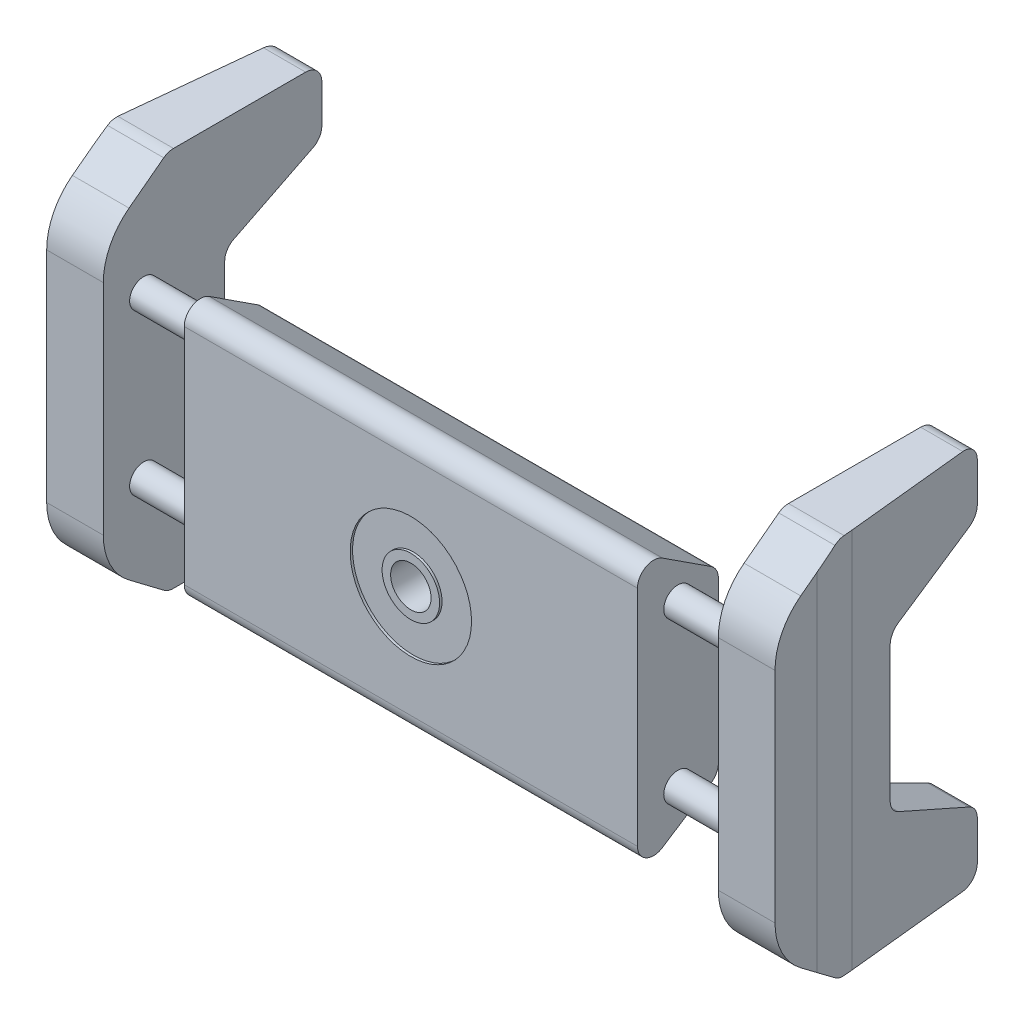
SolidWorks part; units mm, degrees
ref_plane "Front Plane" through (0, 0, 0) normal (0, 0, 1) x (1, 0, 0)
ref_plane "Top Plane" through (0, 0, 0) normal (0, 1, 0) x (1, 0, 0)
ref_plane "Right Plane" through (0, 0, 0) normal (1, 0, 0) x (0, 0, -1)
sketch "Sketch1" plane through (0, 0, 0) normal (1, 0, 0) x (0, 0, -1)
  line L0 (3.09, -2.0085) -> (9.09, -5.9085)
  line L2 (0, -3.6854) -> (0, -31.3146)
  line L4 (10, -7.5854) -> (10, -27.4146)
  line L5 (3.09, -32.9915) -> (9.09, -29.0915)
  arc A0 (3.09, -2.0085) -> (0, -3.6854) centre (2, -3.6854) ccw
  arc A1 (9.09, -5.9085) -> (10, -7.5854) centre (8, -7.5854) cw
  arc A2 (0, -31.3146) -> (3.09, -32.9915) centre (2, -31.3146) ccw
  arc A3 (9.09, -29.0915) -> (10, -27.4146) centre (8, -27.4146) ccw
  point P5 (0, 0)
  point P8 (0, 0)
  point P11 (10, -6.5)
  point P14 (0, -35)
  point P17 (10, -28.5)
  dimension "D1" = 2
  dimension "D2" = 35
  dimension "D3" = 22
extrude "Boss-Extrude1" add sketch "Sketch1" along normal blind 56
sketch "Sketch2" plane through (56, 0, 0) normal (1, 0, 0) x (0, 0, -1)
  line L0 (0, -17.5) -> (10, -17.5) construction
  line L1 (0, -3.6854) -> (0, -31.3146) construction
  line L2 (10, -27.4146) -> (10, -7.5854) construction
  line L3 (5, -32.8793) -> (5, -2.0411) construction
  line L4 (10, -7.5854) -> (0, -7.5854) construction
  circle A0 centre (5, -7.5854) radius 1.75
  circle A1 centre (5, -27.4146) radius 1.75
  dimension "D1" = 3.5
extrude "Boss-Extrude2" add sketch "Sketch2" along normal blind 10
ref_plane "Plane1" through (66, 0, 0) normal (1, 0, 0) x (0, 0, -1)
sketch "Sketch3" plane through (66, 0, 0) normal (1, 0, 0) x (0, 0, -1)
  line L0 (9.09, -5.9085) -> (0, 0) construction
  line L1 (25.8944, -32.4893) -> (16.1056, -27.5948)
  line L2 (10, -7.5854) -> (10, 4.7359) construction
  line L3 (3.1785, 2.4006) -> (7.465, 5.638)
  line L4 (8.6704, 6.0421) -> (25, 6.0421)
  line L5 (27, 4.0421) -> (27, -0.7219)
  line L6 (25.8944, -2.5107) -> (16.1056, -7.4052)
  line L7 (15, -9.194) -> (15, -25.806)
  line L8 (10, -27.4146) -> (10, -7.5854) construction
  line L11 (0, -31.0168) -> (0, -3.9832)
  line L12 (27, -39.0421) -> (27, -34.2781)
  line L13 (8.6704, -41.0421) -> (25, -41.0421)
  line L14 (3.1785, -37.4006) -> (7.465, -40.638)
  arc A0 (16.1056, -7.4052) -> (15, -9.194) centre (17, -9.194) ccw
  arc A1 (7.465, 5.638) -> (8.6704, 6.0421) centre (8.6704, 4.0421) cw
  arc A2 (25, 6.0421) -> (27, 4.0421) centre (25, 4.0421) cw
  arc A3 (27, -0.7219) -> (25.8944, -2.5107) centre (25, -0.7219) cw
  arc A4 (3.1785, 2.4006) -> (0, -3.9832) centre (8, -3.9832) ccw
  arc A5 (16.1056, -27.5948) -> (15, -25.806) centre (17, -25.806) cw
  arc A6 (27, -34.2781) -> (25.8944, -32.4893) centre (25, -34.2781) ccw
  arc A7 (25, -41.0421) -> (27, -39.0421) centre (25, -39.0421) ccw
  arc A8 (7.465, -40.638) -> (8.6704, -41.0421) centre (8.6704, -39.0421) ccw
  arc A9 (3.1785, -37.4006) -> (0, -31.0168) centre (8, -31.0168) cw
  point P22 (15, -7.9579)
  point P25 (8, 6.0421)
  point P28 (27, 6.0421)
  point P31 (27, -1.9579)
  dimension "D6" = 2
  dimension "D7" = 8
  dimension "D1" = 8
  dimension "D2" = 19
  dimension "D3" = 5
  dimension "D4" = 14
  dimension "D5" = 27
extrude "Boss-Extrude3" add sketch "Sketch3" along normal blind 7
sketch "Sketch4" plane through (0, 0, 0) normal (0, 1, 0) x (1, 0, 0)
  line L0 (73, 7.465) -> (71, 27)
  line L1 (73, 27) -> (66, 27) construction
  line L2 (71, 27) -> (73.4889, 29.2177)
  line L3 (73.4889, 29.2177) -> (75.732, 28.8818)
  line L4 (75.732, 28.8818) -> (75.6344, 22.9871)
  line L5 (75.6344, 22.9871) -> (74.6104, 7.6401)
  line L6 (74.6104, 7.6401) -> (73, 7.465)
  dimension "D1" = 2
extrude "Cut-Extrude1" cut sketch "Sketch4" against normal blind 44 and the other way blind 13
fillet "Fillet1" radius 45 1 edges at (73, -17.5, -7.465)
ref_plane "Plane2" through (28, 0, 0) normal (1, 0, 0) x (0, 0, -1)
mirror "Mirror1" about plane through (28, 0, 0) normal (1, 0, 0) of bodies 104
sketch "Sketch5" plane through (0, 0, 0) normal (0, 0, 1) x (1, 0, 0)
  line L0 (28, -3.6854) -> (28, -31.3146) construction
  line L1 (56, -3.6854) -> (0, -3.6854) construction
  line L2 (56, -31.3146) -> (0, -31.3146) construction
  line L3 (0, -17.5) -> (56, -17.5) construction
  line L4 (0, -3.6854) -> (0, -31.3146) construction
  line L5 (56, -3.6854) -> (56, -31.3146) construction
  circle A0 centre (28, -17.5) radius 2.5
  dimension "D1" = 5
extrude "Cut-Extrude2" cut sketch "Sketch5" against normal blind 44 and the other way blind 44
sketch "Sketch6" plane through (0, 0, -10) normal (0, 0, -1) x (-1, 0, 0)
  circle A0 centre (-28, -17.5) radius 5
  dimension "D1" = 10
extrude "Cut-Extrude3" cut sketch "Sketch6" against normal blind 1 draft 66
sketch "Sketch7" plane through (0, 0, 0) normal (0, 0, 1) x (1, 0, 0)
  line L0 (29.1859, -14.364) -> (28.9738, -14.9817)
  line L2 (28.1034, -14.1489) -> (28.1034, -14.802)
  line L4 (28.3034, -14.161) -> (28.3034, -14.8171)
  line L5 (29.3711, -14.4404) -> (29.1581, -15.061)
  line L6 (30.1399, -14.919) -> (29.7387, -15.4344)
  line L7 (30.2902, -15.0514) -> (29.8873, -15.5691)
  line L8 (30.862, -15.7536) -> (30.3152, -16.1108)
  line L9 (30.9612, -15.9277) -> (30.412, -16.2865)
  line L10 (31.274, -16.7775) -> (30.6408, -16.9379)
  line L11 (31.3113, -16.9744) -> (30.6753, -17.1355)
  line L12 (31.3311, -17.8797) -> (30.6803, -17.8258)
  line L13 (31.3025, -18.078) -> (30.6487, -18.0239)
  line L14 (31.0274, -18.9408) -> (30.4293, -18.6784)
  line L15 (30.9359, -19.119) -> (30.3351, -18.8555)
  line L16 (30.3955, -19.8457) -> (29.915, -19.4034)
  line L17 (30.2511, -19.9846) -> (29.7684, -19.5403)
  line L18 (29.5041, -20.4964) -> (29.1932, -19.922)
  line L19 (29.3224, -20.5809) -> (29.0101, -20.0039)
  line L20 (28.4496, -20.8224) -> (28.3421, -20.1782)
  line L21 (28.2504, -20.8434) -> (28.1424, -20.1962)
  line L22 (27.3465, -20.7884) -> (27.454, -20.1442)
  line L23 (27.1512, -20.7435) -> (27.2592, -20.0964)
  line L24 (26.3141, -20.398) -> (26.625, -19.8236)
  line L25 (26.144, -20.2922) -> (26.4563, -19.7152)
  line L26 (25.4645, -19.6936) -> (25.945, -19.2513)
  line L27 (25.338, -19.5382) -> (25.8207, -19.0939)
  line L28 (24.8896, -18.7515) -> (25.4877, -18.4891)
  line L29 (24.8204, -18.5634) -> (25.4212, -18.2999)
  line L30 (24.6518, -17.6737) -> (25.3027, -17.6198)
  line L31 (24.6474, -17.4734) -> (25.3012, -17.4192)
  line L32 (24.7768, -16.5772) -> (25.4099, -16.7375)
  line L33 (24.8377, -16.3863) -> (25.4737, -16.5473)
  line L34 (25.2511, -15.5806) -> (25.7978, -15.9378)
  line L35 (25.3706, -15.4198) -> (25.9199, -15.7786)
  line L36 (26.0233, -14.792) -> (26.4244, -15.3074)
  line L37 (26.1886, -14.6788) -> (26.5915, -15.1965)
  line L38 (27.0096, -14.2969) -> (27.2217, -14.9146)
  line L39 (27.2028, -14.2435) -> (27.4158, -14.864)
  circle A0 centre (28, -17.5) radius 7.5
  circle A1 centre (28, -17.5) radius 3.5527
  arc A2 (28.1034, -14.1489) -> (27.2028, -14.2435) centre (28, -17.5) ccw
  arc A3 (27.454, -20.1442) -> (28.1424, -20.1962) centre (28, -17.5) ccw
  arc A4 (26.4244, -15.3074) -> (25.9199, -15.7786) centre (28, -17.5) ccw
  circle A5 centre (28, -17.5) radius 2.7
  arc A6 (28.1034, -14.802) -> (27.4158, -14.864) centre (28, -17.5) ccw
  circle A7 centre (28, -17.5) radius 3.3527 construction
  arc A8 (27.2217, -14.9146) -> (26.5915, -15.1965) centre (28, -17.5) ccw
  arc A9 (28.9738, -14.9817) -> (28.3034, -14.8171) centre (28, -17.5) ccw
  arc A10 (29.1859, -14.364) -> (28.3034, -14.161) centre (28, -17.5) ccw
  arc A11 (27.0096, -14.2969) -> (26.1886, -14.6788) centre (28, -17.5) ccw
  arc A12 (26.0233, -14.792) -> (25.3706, -15.4198) centre (28, -17.5) ccw
  arc A13 (25.2511, -15.5806) -> (24.8377, -16.3863) centre (28, -17.5) ccw
  arc A14 (25.7978, -15.9378) -> (25.4737, -16.5473) centre (28, -17.5) ccw
  arc A15 (25.4099, -16.7375) -> (25.3012, -17.4192) centre (28, -17.5) ccw
  arc A16 (24.7768, -16.5772) -> (24.6474, -17.4734) centre (28, -17.5) ccw
  arc A17 (24.6518, -17.6737) -> (24.8204, -18.5634) centre (28, -17.5) ccw
  arc A18 (25.3027, -17.6198) -> (25.4212, -18.2999) centre (28, -17.5) ccw
  arc A19 (25.4877, -18.4891) -> (25.8207, -19.0939) centre (28, -17.5) ccw
  arc A20 (24.8896, -18.7515) -> (25.338, -19.5382) centre (28, -17.5) ccw
  arc A21 (25.945, -19.2513) -> (26.4563, -19.7152) centre (28, -17.5) ccw
  arc A22 (25.4645, -19.6936) -> (26.144, -20.2922) centre (28, -17.5) ccw
  arc A23 (26.625, -19.8236) -> (27.2592, -20.0964) centre (28, -17.5) ccw
  arc A24 (26.3141, -20.398) -> (27.1512, -20.7435) centre (28, -17.5) ccw
  arc A25 (27.3465, -20.7884) -> (28.2504, -20.8434) centre (28, -17.5) ccw
  arc A26 (28.3421, -20.1782) -> (29.0101, -20.0039) centre (28, -17.5) ccw
  arc A27 (28.4496, -20.8224) -> (29.3224, -20.5809) centre (28, -17.5) ccw
  arc A28 (29.5041, -20.4964) -> (30.2511, -19.9846) centre (28, -17.5) ccw
  arc A29 (29.1932, -19.922) -> (29.7684, -19.5403) centre (28, -17.5) ccw
  arc A30 (30.3955, -19.8457) -> (30.9359, -19.119) centre (28, -17.5) ccw
  arc A31 (29.915, -19.4034) -> (30.3351, -18.8555) centre (28, -17.5) ccw
  arc A32 (30.4293, -18.6784) -> (30.6487, -18.0239) centre (28, -17.5) ccw
  arc A33 (31.0274, -18.9408) -> (31.3025, -18.078) centre (28, -17.5) ccw
  arc A34 (30.6803, -17.8258) -> (30.6753, -17.1355) centre (28, -17.5) ccw
  arc A35 (31.3311, -17.8797) -> (31.3113, -16.9744) centre (28, -17.5) ccw
  arc A36 (31.274, -16.7775) -> (30.9612, -15.9277) centre (28, -17.5) ccw
  arc A37 (30.6408, -16.9379) -> (30.412, -16.2865) centre (28, -17.5) ccw
  arc A38 (30.862, -15.7536) -> (30.2902, -15.0514) centre (28, -17.5) ccw
  arc A39 (30.3152, -16.1108) -> (29.8873, -15.5691) centre (28, -17.5) ccw
  arc A40 (30.1399, -14.919) -> (29.3711, -14.4404) centre (28, -17.5) ccw
  arc A41 (29.7387, -15.4344) -> (29.1581, -15.061) centre (28, -17.5) ccw
  point P13 (31.2062, -16.5198)
  dimension "D1" = 15
  dimension "D4" = 19
  dimension "D2" = 0.2
  dimension "D3" = 0.2
extrude "Cut-Extrude4" cut sketch "Sketch7" against normal blind 0.3 contours A0 | A1
